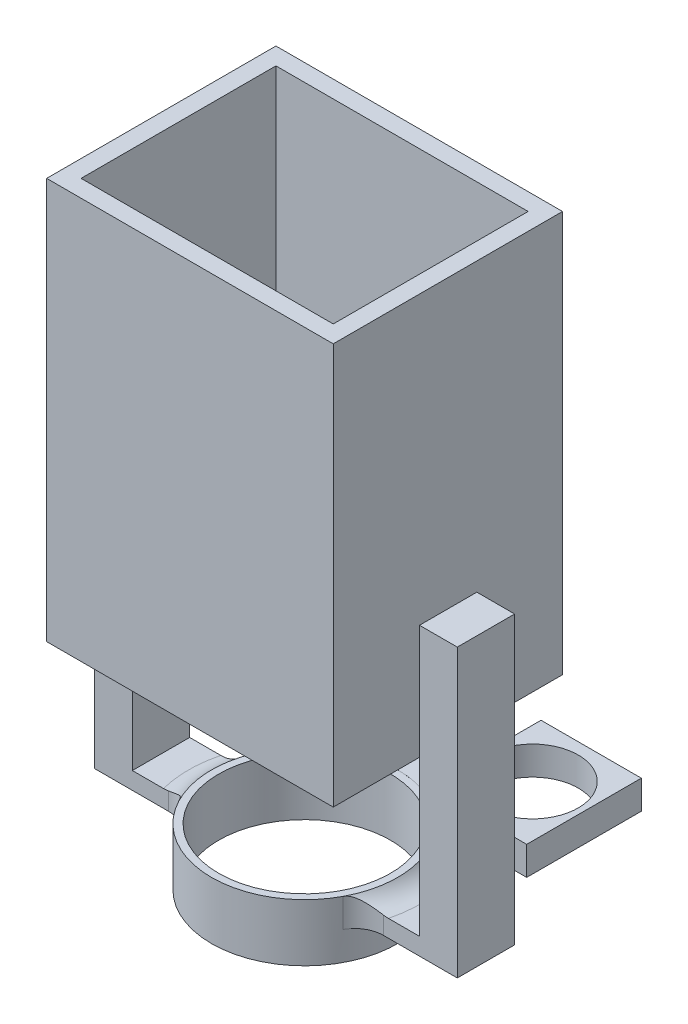
SolidWorks part; units mm, degrees
ref_plane "Front Plane" through (0, 0, 0) normal (0, 0, 1) x (1, 0, 0)
ref_plane "Top Plane" through (0, 0, 0) normal (0, 1, 0) x (1, 0, 0)
ref_plane "Right Plane" through (0, 0, 0) normal (1, 0, 0) x (0, 0, -1)
sketch "Sketch2" plane through (0, 0, 0) normal (0, 1, 0) x (1, 0, 0)
  line L0 (0, 15) -> (0, -15) construction
  line L1 (-15, 0) -> (15, 0) construction
  line L2 (-15, 0) -> (-15, 5) construction
  line L3 (-14.1421, 5) -> (-31.6421, 5)
  line L4 (-31.6421, 5) -> (-31.6421, -5)
  line L5 (-14.1421, -5) -> (-31.6421, -5)
  line L6 (14.1421, -5) -> (31.6421, -5)
  line L7 (31.6421, 5) -> (31.6421, -5)
  line L8 (14.1421, 5) -> (31.6421, 5)
  line L9 (0, 16.25) -> (22.5, 16.25)
  line L10 (22.5, 16.25) -> (22.5, 36.25)
  line L11 (22.5, 36.25) -> (5, 36.25)
  line L12 (-22.5, 36.25) -> (-22.5, 16.25)
  line L13 (-22.5, 16.25) -> (0, 16.25)
  line L14 (22.5, 26.25) -> (21.5, 26.25) construction
  line L20 (-5, 36.25) -> (-22.5, 36.25)
  line L21 (0, 31.25) -> (0, 16.25) construction
  line L22 (-5, 36.25) -> (-5, 31.25)
  line L23 (-5, 31.25) -> (5, 31.25)
  line L24 (5, 31.25) -> (5, 36.25)
  line L25 (13.5, 34.25) -> (13.5, 36.25) construction
  line L26 (13.5, 18.25) -> (13.5, 16.25) construction
  line L27 (-13.5, 26.25) -> (13.5, 26.25) construction
  line L28 (-13.5, 9.045) -> (-13.5, 16.25)
  line L29 (13.5, 16.25) -> (13.5, 9.045)
  line L30 (-16.25, 0) -> (-25.05, 0) construction
  line L31 (-25.05, 5) -> (-25.05, -5)
  line L32 (25.05, 5) -> (25.05, -5)
  circle A0 centre (0, 0) radius 15
  circle A1 centre (0, 0) radius 16.25
  circle A2 centre (13.5, 26.25) radius 8
  circle A3 centre (-13.5, 26.25) radius 8
  point P13 (-31.6421, 0)
  dimension "D1" = 30
  dimension "D2" = 17.5
  dimension "D4" = 32.5
  dimension "D8" = 1
  dimension "D9" = 16
  dimension "D3" = 5
  dimension "D5" = 5
  dimension "D6" = 20
  dimension "D7" = 45
  dimension "D10" = 17.5
  dimension "D11" = 8.8
extrude "Connector sleeve" add sketch "Sketch2" along normal blind 5 and the other way blind 5 contours L5 A1 L6 A0 | L8 A1 L3 A0 | L6 A1 L8 A0 | L3 A1 L5 A0 region at (-14.3253, 0, -6.9471) region at (-15.3497, 0, 0) region at (-14.8019, 0, 5.3291) region at (15.3497, 0, 0)
ref_plane "Plane2" through (0, 30, 0) normal (0, 1, 0) x (1, 0, 0)
sketch "Sketch3" plane through (0, 30, 0) normal (0, 1, 0) x (1, 0, 0)
  line L1 (-25, 20) -> (25, 20)
  line L2 (-25, 20) -> (-25, -20)
  line L3 (-25, -20) -> (25, -20)
  line L4 (25, 20) -> (25, -20)
  line L5 (-25, 20) -> (25, -20) construction
  line L6 (-25, -20) -> (25, 20) construction
  circle A0 centre (0, 0) radius 3
  point P0 (0, 0)
  dimension "D3" = 6
  dimension "D1" = 50
  dimension "D2" = 40
extrude "Motor casing" add sketch "Sketch3" along normal blind 70
shell "Shell4" thickness 3 removed face at (0, 100, 3) removed face at (0, 100, 0)
sketch "Sketch6" plane through (0, 33, 0) normal (0, 1, 0) x (1, 0, 0)
  circle A0 centre (0, 0) radius 15
  circle A1 centre (0, 0) radius 16
  dimension "D1" = 30
  dimension "D2" = 32
extrude "Motor sits here" add sketch "Sketch6" along normal blind 30
extrude "Sleeve-casing connector" add sketch "Sketch2<16>" along normal blind 3 contours A1 L3 L31 L5 | L31 L3 L4 L5 | A1 L6 L32 L8 | L8 L32 L6 L7 region at (-28.3461, 0, 0) region at (-20.5169, 0, 0) region at (20.5169, 0, 0) region at (28.3461, 0, 0)
sketch "Sketch2<16>" plane through (0, 0, 0) normal (0, 1, 0) x (1, 0, 0) same geometry as "Sketch2"
extrude "Sleeve-casing arms" add sketch "Sketch2<17>" along normal blind 50 contours L31 L3 L4 L5 | L8 L32 L6 L7 region at (-28.3461, 0, 0) region at (28.3461, 0, 0)
sketch "Sketch2<17>" plane through (0, 0, 0) normal (0, 1, 0) x (1, 0, 0) same geometry as "Sketch2"
extrude "Sensor holder" add sketch "Sketch2<10>" along normal blind 5 separate body contours L24 L23 L22 L20 L12 L13 L9 L10 L11 A2 A3 | A1 L13 L28 | A1 L29 L9 region at (-10.2927, 0, -14.2057) region at (0, 0, -25.4127) region at (10.2927, 0, -14.2057)
sketch "Sketch2<10>" plane through (0, 0, 0) normal (0, 1, 0) x (1, 0, 0) same geometry as "Sketch2"
fillet "Fillet2" radius 5 6 edges at (-15.4616, 1.5, -5) (-16.25, 3, 0) (-15.4616, 1.5, 5) (15.4616, 1.5, 5) (15.4616, 1.5, -5) (16.25, 3, 0)
